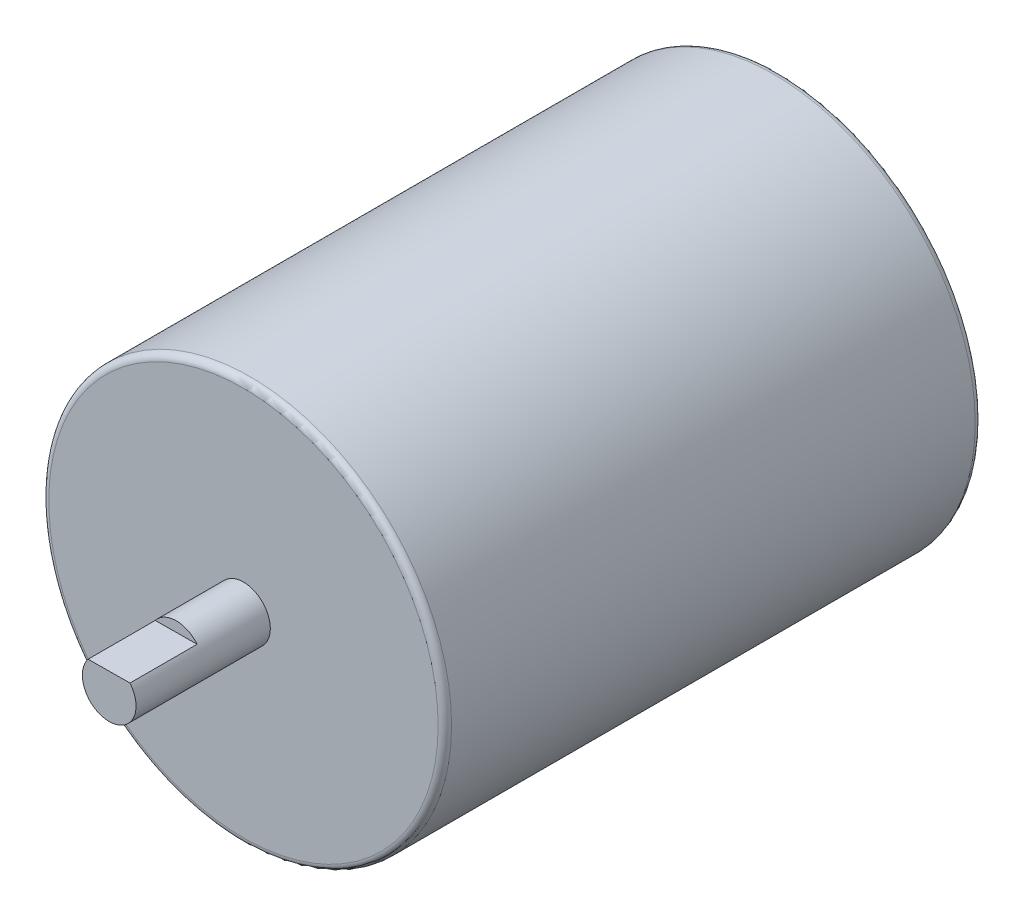
SolidWorks part; units mm, degrees
ref_plane "Plan de face" through (0, 0, 0) normal (1, 0, 0) x (0, 1, 0)
ref_plane "Plan de dessus" through (0, 0, 0) normal (0, 0, 1) x (0, 1, 0)
ref_plane "Plan de droite" through (0, 0, 0) normal (0, 1, 0) x (-1, 0, 0)
sketch "Esquisse1" plane through (0, 0, 0) normal (0, 0, 1) x (0, 1, 0)
  circle A0 centre (0, 0) radius 30
  dimension "D1" = 60
extrude "Boss.-Extru.1" add sketch "Esquisse1" along normal blind 80
sketch "Esquisse2" plane through (0, 0, 80) normal (0, 0, 1) x (1, 0, 0)
  circle A0 centre (0, 0) radius 4
  dimension "D1" = 8
extrude "Boss.-Extru.2" add sketch "Esquisse2" along normal blind 20
sketch "Esquisse3" plane through (0, 0, 100) normal (0, 0, 1) x (1, 0, 0)
  line L0 (-3.1427, 2.4746) -> (3.102, 2.5254)
  arc A0 (-3.1427, 2.4746) -> (3.102, 2.5254) centre (0, 0) cw
  circle A1 centre (0, 0) radius 4 construction
  point P6 (-0.0203, 2.5)
  dimension "D1" = 2.5
extrude "Enlèv. mat.-Extru.1" cut sketch "Esquisse3" against normal blind 10
fillet "Congé1" radius 1 2 edges at (30, 0, 0) (30, 0, 80)
